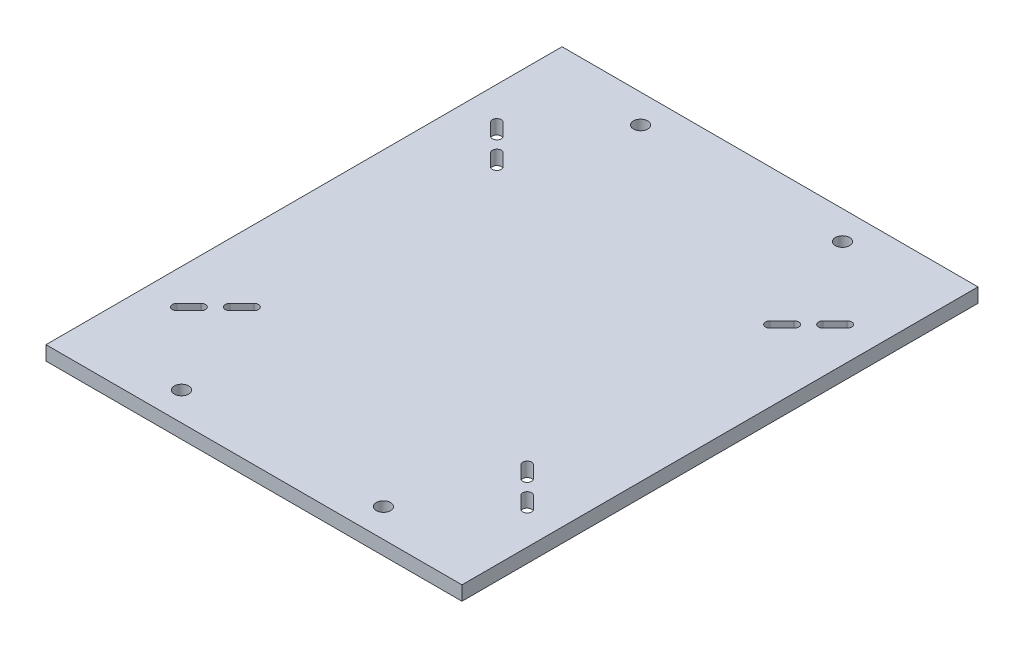
SolidWorks part; units mm, degrees
material "6061-T6 (SS)"
ref_plane "Front Plane" through (0, 0, 0) normal (0, 0, 1) x (1, 0, 0)
ref_plane "Top Plane" through (0, 0, 0) normal (0, 1, 0) x (1, 0, 0)
ref_plane "Right Plane" through (0, 0, 0) normal (1, 0, 0) x (0, 0, -1)
sketch "Sketch1" plane through (0, 0, 0) normal (0, 1, 0) x (1, 0, 0)
  line L1 (0, 0) -> (185.4, 0)
  line L2 (0, 0) -> (0, -230)
  line L3 (0, -230) -> (185.4, -230)
  line L4 (185.4, 0) -> (185.4, -230)
  dimension "D1" = 185.4
  dimension "D2" = 230
extrude "base plate" add sketch "Sketch1" against normal blind 6.35
sketch "center lines" plane through (0, 0, 0) normal (0, 1, 0) x (1, 0, 0)
  line L0 (92.7, 0) -> (92.7, -230) construction
  line L1 (185.4, 0) -> (0, 0) construction
  line L2 (0, -230) -> (185.4, -230) construction
  line L3 (0, -115) -> (185.4, -115) construction
  line L4 (0, 0) -> (0, -230) construction
  line L5 (185.4, -230) -> (185.4, 0) construction
sketch "Sketch3" plane through (0, 0, 0) normal (0, 1, 0) x (1, 0, 0)
  line L0 (1.825, -188.3487) -> (12.6013, -199.125)
  line L1 (12.6013, -199.125) -> (46.7263, -165)
  line L2 (46.7263, -165) -> (35.95, -154.2237)
  line L3 (35.95, -154.2237) -> (1.825, -188.3487)
  line L4 (14.6222, -186.3278) -> (20.0104, -180.9396) construction
  line L5 (13.208, -184.9135) -> (18.5962, -179.5254)
  line L6 (16.0365, -187.742) -> (21.4246, -182.3538)
  line L7 (0, -230) -> (185.4, -230) construction
  line L8 (31.8191, -169.1309) -> (26.4309, -174.5191) construction
  line L9 (33.2333, -170.5451) -> (27.8451, -175.9333)
  line L10 (92.7, 0) -> (92.7, -230) construction
  line L11 (0, -115) -> (185.4, -115) construction
  line L12 (46.7263, -65) -> (35.95, -75.7763)
  line L13 (12.6013, -30.875) -> (46.7263, -65)
  line L14 (1.825, -41.6513) -> (12.6013, -30.875)
  line L15 (35.95, -75.7763) -> (1.825, -41.6513)
  line L16 (172.7987, -30.875) -> (138.6737, -65)
  line L17 (183.575, -41.6513) -> (172.7987, -30.875)
  line L18 (149.45, -75.7763) -> (183.575, -41.6513)
  line L19 (138.6737, -65) -> (149.45, -75.7763)
  line L20 (138.6737, -165) -> (149.45, -154.2237)
  line L21 (172.7987, -199.125) -> (138.6737, -165)
  line L22 (183.575, -188.3487) -> (172.7987, -199.125)
  line L23 (149.45, -154.2237) -> (183.575, -188.3487)
  line L24 (30.4049, -167.7167) -> (25.0167, -173.1049)
  line L25 (14.6222, -43.6722) -> (20.0104, -49.0604) construction
  line L26 (13.208, -45.0865) -> (18.5962, -50.4746)
  line L27 (16.0365, -42.258) -> (21.4246, -47.6462)
  line L28 (31.8191, -60.8691) -> (26.4309, -55.4809) construction
  line L29 (33.2333, -59.4549) -> (27.8451, -54.0667)
  line L30 (30.4049, -62.2833) -> (25.0167, -56.8951)
  line L31 (170.7778, -43.6722) -> (165.3896, -49.0604) construction
  line L32 (172.192, -45.0865) -> (166.8038, -50.4746)
  line L33 (169.3635, -42.258) -> (163.9754, -47.6462)
  line L34 (153.5809, -60.8691) -> (158.9691, -55.4809) construction
  line L35 (152.1667, -59.4549) -> (157.5549, -54.0667)
  line L36 (154.9951, -62.2833) -> (160.3833, -56.8951)
  line L37 (153.5809, -169.1309) -> (158.9691, -174.5191) construction
  line L38 (152.1667, -170.5451) -> (157.5549, -175.9333)
  line L39 (154.9951, -167.7167) -> (160.3833, -173.1049)
  line L40 (170.7778, -186.3278) -> (165.3896, -180.9396) construction
  line L41 (172.192, -184.9135) -> (166.8038, -179.5254)
  line L42 (169.3635, -187.742) -> (163.9754, -182.3538)
  line L43 (35.95, -165) -> (35.95, -154.2237)
  line L44 (46.7263, -165) -> (35.95, -165)
  line L45 (35.95, -65) -> (35.95, -75.7763)
  line L46 (46.7263, -65) -> (35.95, -65)
  line L47 (149.45, -65) -> (149.45, -75.7763)
  line L48 (138.6737, -65) -> (149.45, -65)
  line L49 (149.45, -165) -> (149.45, -154.2237)
  line L50 (138.6737, -165) -> (149.45, -165)
  line L53 (185.4, 0) -> (0, 0) construction
  arc A0 (13.208, -184.9135) -> (16.0365, -187.742) centre (14.6222, -186.3278) ccw
  arc A1 (21.4246, -182.3538) -> (18.5962, -179.5254) centre (20.0104, -180.9396) ccw
  arc A2 (33.2333, -170.5451) -> (30.4049, -167.7167) centre (31.8191, -169.1309) ccw
  arc A3 (25.0167, -173.1049) -> (27.8451, -175.9333) centre (26.4309, -174.5191) ccw
  arc A4 (13.208, -45.0865) -> (16.0365, -42.258) centre (14.6222, -43.6722) cw
  arc A5 (21.4246, -47.6462) -> (18.5962, -50.4746) centre (20.0104, -49.0604) cw
  arc A6 (33.2333, -59.4549) -> (30.4049, -62.2833) centre (31.8191, -60.8691) cw
  arc A7 (25.0167, -56.8951) -> (27.8451, -54.0667) centre (26.4309, -55.4809) cw
  arc A8 (172.192, -45.0865) -> (169.3635, -42.258) centre (170.7778, -43.6722) ccw
  arc A9 (163.9754, -47.6462) -> (166.8038, -50.4746) centre (165.3896, -49.0604) ccw
  arc A10 (152.1667, -59.4549) -> (154.9951, -62.2833) centre (153.5809, -60.8691) ccw
  arc A11 (160.3833, -56.8951) -> (157.5549, -54.0667) centre (158.9691, -55.4809) ccw
  arc A12 (152.1667, -170.5451) -> (154.9951, -167.7167) centre (153.5809, -169.1309) cw
  arc A13 (160.3833, -173.1049) -> (157.5549, -175.9333) centre (158.9691, -174.5191) cw
  arc A14 (172.192, -184.9135) -> (169.3635, -187.742) centre (170.7778, -186.3278) cw
  arc A15 (163.9754, -182.3538) -> (166.8038, -179.5254) centre (165.3896, -180.9396) cw
  point P29 (17.3163, -183.6337)
  point P36 (29.125, -171.825)
  point P44 (17.3163, -46.3663)
  point P51 (29.125, -58.175)
  point P58 (168.0837, -46.3663)
  point P65 (156.275, -58.175)
  point P72 (156.275, -171.825)
  point P79 (168.0837, -183.6337)
  point P84 (21.4246, -179.5254)
  point P85 (25.0167, -175.9333)
  dimension "D6" = 2
  dimension "D10" = 5.08
  dimension "D9" = 5.842
  dimension "D1" = 48.26
  dimension "D2" = 15.24
  dimension "D3" = 45
  dimension "D4" = 100
  dimension "D5" = 113.5
  dimension "D7" = 7.62
  dimension "D8" = 7.62
extrude "slots" cut sketch "Sketch3" against normal through all contours A5 L27 A4 L26 | L33 A9 L32 A8 | L36 A11 L35 A10 | A13 L39 A12 L38 | A15 L42 A14 L41 | L6 A1 L5 A0 | L24 A3 L9 A2 | L30 A7 L29 A6 region at (17.3163, 0, 46.3663) region at (168.0837, 0, 46.3663) region at (156.275, 0, 58.175) region at (156.275, 0, 171.825) region at (168.0837, 0, 183.6337)
hole_wizard "Feet connection hole" positions "Sketch6" profile "Sketch7" hole size "1/4" standard "ANSI Inch" end condition through all
sketch "Sketch6" plane through (0, 0, 0) normal (0, 1, 0) x (1, 0, 0)
  line L0 (0, -230) -> (185.4, -230) construction
  line L3 (185.4, 0) -> (0, 0) construction
  line L4 (92.7, 0) -> (92.7, -230) construction
  point P3 (47.7, -217.3)
  point P19 (137.7, -12.7)
  point P33 (47.7, -12.7)
  point P37 (137.7, -217.3)
  dimension "D1" = 12.7
  dimension "D2" = 90
  dimension "D3" = 45
  dimension "D4" = 12.7
sketch "Sketch7" plane through (47.7, 0, 217.3) normal (1, 0, 0) x (0, 0, 1)
  line L0 (0, 0) -> (0, 6.35)
  line L1 (0, 6.35) -> (3.175, 6.35)
  line L2 (3.175, 6.35) -> (3.175, 0)
  line L5 (3.175, 0) -> (0, 0)
  line L11 (0, -6.35) -> (0, 107.95) construction
  dimension "Thru Hole Dia." = 6.35
  dimension "Thru Hole Depth" = 6.35
ref_plane "Center Plane" through (0, 0, 115) normal (0, 0, 1) x (1, 0, 0)
